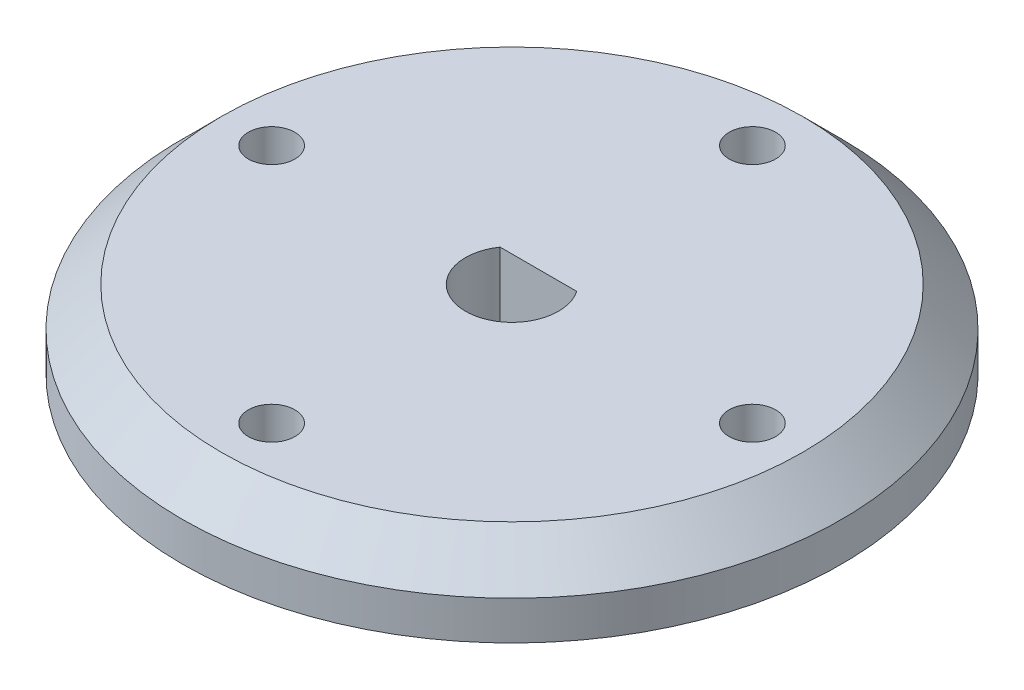
SolidWorks part; units mm, degrees
ref_plane "Front Plane" through (0, 0, 0) normal (0, 0, 1) x (1, 0, 0)
ref_plane "Top Plane" through (0, 0, 0) normal (0, 1, 0) x (1, 0, 0)
ref_plane "Right Plane" through (0, 0, 0) normal (1, 0, 0) x (0, 0, -1)
sketch "Sketch1" plane through (0, 0, 0) normal (0, 1, 0) x (1, 0, 0)
  line L0 (-2.4718, 1.7) -> (2.4718, 1.7)
  line L1 (0, 0) -> (0, -3) construction
  circle A0 centre (0, 0) radius 21.25
  circle A1 centre (0, 0) radius 15.5 construction
  circle A2 centre (0, 0) radius 3 construction
  circle A3 centre (0, 15.5) radius 1.5
  circle A4 centre (15.5, 0) radius 1.5
  circle A5 centre (0, -15.5) radius 1.5
  circle A6 centre (-15.5, 0) radius 1.5
  arc A7 (-2.4718, 1.7) -> (2.4718, 1.7) centre (0, 0) ccw
  dimension "D1" = 6
  dimension "D2" = 31
  dimension "D3" = 42.5
  dimension "D4" = 3
  dimension "D5" = 4.7
extrude "Boss-Extrude1" add sketch "Sketch1" along normal blind 5
chamfer "Chamfer1" distance 2.5 angle 45 1 edges at (0, 5, 21.25)
